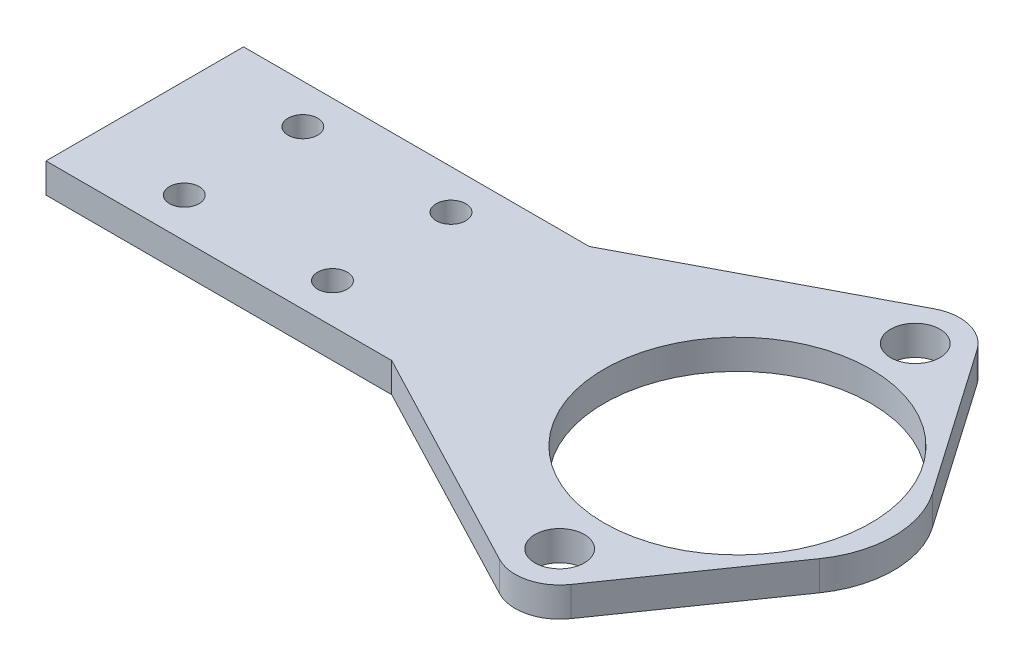
SolidWorks part; units mm, degrees
material "Thornel Mat VMA"
ref_plane "前视基准面" through (0, 0, 0) normal (0, 0, 1) x (1, 0, 0)
ref_plane "上视基准面" through (0, 0, 0) normal (0, 1, 0) x (1, 0, 0)
ref_plane "右视基准面" through (0, 0, 0) normal (1, 0, 0) x (0, 0, -1)
sketch "草图1" plane through (0, 0, 0) normal (0, 1, 0) x (1, 0, 0)
  line L0 (-26.9883, 20) -> (-4.0741, 31.9874)
  line L1 (-61.9883, 20) -> (-26.9883, 20)
  line L2 (-61.9883, 20) -> (-61.9883, 0)
  line L3 (-61.9883, 0) -> (-26.9883, 0)
  line L5 (-26.9883, 0) -> (-4.074, -11.987)
  line L6 (-1.9883, 10.0004) -> (16.0117, 10.0004)
  line L7 (12.0406, 15.7101) -> (1.7058, 30.5696)
  line L8 (12.0407, 4.2906) -> (1.7063, -10.569)
  circle A0 centre (-36.9883, 16) radius 1.5
  circle A1 centre (-51.9883, 16) radius 1.5
  circle A2 centre (-36.9883, 4) radius 1.5
  circle A3 centre (-51.9883, 4) radius 1.5
  circle A4 centre (-1.9883, 10.0004) radius 13.5
  circle A5 centre (-1.9883, 28.0004) radius 2.5
  circle A6 centre (-1.9881, -7.9996) radius 2.5
  arc A7 (1.7058, 30.5696) -> (-4.0741, 31.9874) centre (-1.9883, 28.0004) ccw
  arc A8 (-4.074, -11.987) -> (1.7063, -10.569) centre (-1.9881, -7.9996) ccw
  arc A9 (12.0406, 15.7101) -> (12.0407, 4.2906) centre (3.831, 10.0003) cw
  dimension "D2" = 25
  dimension "D3" = 4
  dimension "D4" = 15
  dimension "D5" = 12
  dimension "D6" = 60
  dimension "D7" = 27
  dimension "D9" = 18
  dimension "D12" = 10
  dimension "D1" = 20
  dimension "D8" = 18
  dimension "D11" = 18
extrude "凸台-拉伸1" add sketch "草图1" along normal blind 3 contours A9 L7 A7 L0 L1 L2 L3 L5 A8 L8 A4 A6 A5 A3 A2 A1 A0 region at (-28.1454, 0, -10)
